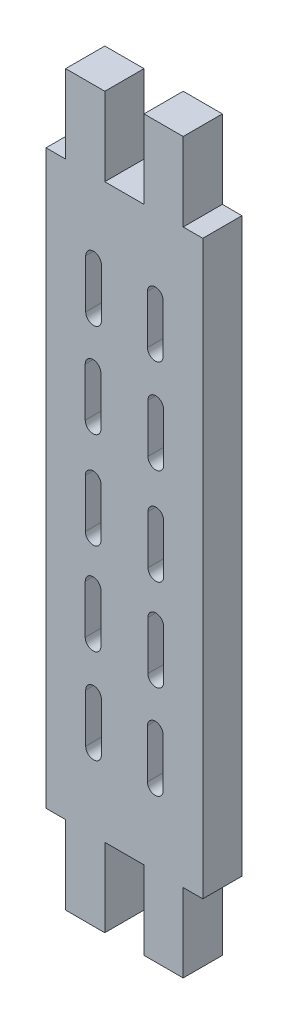
SolidWorks part; units mm, degrees
ref_plane "Front Plane" through (0, 0, 0) normal (0, 0, 1) x (1, 0, 0)
ref_plane "Top Plane" through (0, 0, 0) normal (0, 1, 0) x (1, 0, 0)
ref_plane "Right Plane" through (0, 0, 0) normal (1, 0, 0) x (0, 0, -1)
sketch "Sketch1" plane through (0, 0, 0) normal (0, 0, 1) x (1, 0, 0)
  line L0 (-7.5, 36.5) -> (-7.5, 46.5)
  line L1 (-10, -36.5) -> (-7.5, -36.5)
  line L2 (-10, -36.5) -> (-10, 36.5)
  line L3 (-10, 36.5) -> (-7.5, 36.5)
  line L4 (10, -36.5) -> (10, 36.5)
  line L5 (-10, -36.5) -> (10, 36.5) construction
  line L6 (-10, 36.5) -> (10, -36.5) construction
  line L7 (-7.5, 46.5) -> (-2.5, 46.5)
  line L8 (-2.5, 46.5) -> (-2.5, 36.5)
  line L9 (2.5, 36.5) -> (2.5, 46.5)
  line L10 (2.5, 46.5) -> (7.5, 46.5)
  line L11 (7.5, 46.5) -> (7.5, 36.5)
  line L12 (-2.5, 36.5) -> (2.5, 36.5)
  line L13 (7.5, 36.5) -> (10, 36.5)
  line L14 (-2.5, -36.5) -> (2.5, -36.5)
  line L16 (-7.5, -36.5) -> (-7.5, -41.5)
  line L20 (2.5, -36.5) -> (2.5, -46.5)
  line L23 (7.5, -36.5) -> (10, -36.5)
  line L24 (-7.5, -41.5) -> (-7.5, -46.5)
  line L25 (-7.5, -46.5) -> (-2.5, -46.5)
  line L26 (-2.5, -46.5) -> (-2.5, -36.5)
  line L28 (2.5, -46.5) -> (7.5, -46.5)
  line L29 (7.5, -46.5) -> (7.5, -36.5)
  line L30 (0, 0) -> (0, 42.4958) construction
  line L31 (0, 0) -> (41.6146, 0) construction
  line L32 (4, -15.1) -> (4, -8.9) construction
  line L35 (3, -15.1) -> (3, -8.9)
  line L38 (5, -15.1) -> (5, -8.9)
  line L41 (4, 15.1) -> (4, 8.9) construction
  line L44 (3, 15.1) -> (3, 8.9)
  line L51 (5, 15.1) -> (5, 8.9)
  line L52 (-4, 15.1) -> (-4, 8.9) construction
  line L53 (-3, 15.1) -> (-3, 8.9)
  line L54 (-5, 15.1) -> (-5, 8.9)
  line L55 (-4, -15.1) -> (-4, -8.9) construction
  line L56 (-3, -15.1) -> (-3, -8.9)
  line L57 (-5, -15.1) -> (-5, -8.9)
  line L58 (3.9391, 27.1) -> (3.9391, 20.9) construction
  line L61 (2.9391, 27.1) -> (2.9391, 20.9)
  line L64 (4.9391, 27.1) -> (4.9391, 20.9)
  line L67 (-3.9391, 27.1) -> (-3.9391, 20.9) construction
  line L68 (-2.9391, 27.1) -> (-2.9391, 20.9)
  line L69 (-4.9391, 27.1) -> (-4.9391, 20.9)
  line L70 (4.0117, 2.8029) -> (4.0117, -3.3971) construction
  line L71 (3.0117, 2.8029) -> (3.0117, -3.3971)
  line L72 (5.0117, 2.8029) -> (5.0117, -3.3971)
  line L73 (-3.9883, 2.8029) -> (-3.9883, -3.3971) construction
  line L74 (-2.9883, 2.8029) -> (-2.9883, -3.3971)
  line L75 (-4.9883, 2.8029) -> (-4.9883, -3.3971)
  line L76 (3.9391, -27.1) -> (3.9391, -20.9) construction
  line L77 (2.9391, -27.1) -> (2.9391, -20.9)
  line L78 (4.9391, -27.1) -> (4.9391, -20.9)
  line L79 (-3.9391, -27.1) -> (-3.9391, -20.9) construction
  line L80 (-2.9391, -27.1) -> (-2.9391, -20.9)
  line L81 (-4.9391, -27.1) -> (-4.9391, -20.9)
  line L82 (3.9391, 24) -> (21.2063, 24) construction
  line L83 (4, 12) -> (20.2276, 12) construction
  arc A29 (3, -15.1) -> (5, -15.1) centre (4, -15.1) ccw
  arc A30 (5, -8.9) -> (3, -8.9) centre (4, -8.9) ccw
  arc A33 (3, 15.1) -> (5, 15.1) centre (4, 15.1) cw
  arc A34 (5, 8.9) -> (3, 8.9) centre (4, 8.9) cw
  arc A35 (-3, 15.1) -> (-5, 15.1) centre (-4, 15.1) ccw
  arc A36 (-5, 8.9) -> (-3, 8.9) centre (-4, 8.9) ccw
  arc A37 (-3, -15.1) -> (-5, -15.1) centre (-4, -15.1) cw
  arc A38 (-5, -8.9) -> (-3, -8.9) centre (-4, -8.9) cw
  arc A45 (2.9391, 27.1) -> (4.9391, 27.1) centre (3.9391, 27.1) cw
  arc A46 (4.9391, 20.9) -> (2.9391, 20.9) centre (3.9391, 20.9) cw
  arc A47 (-2.9391, 27.1) -> (-4.9391, 27.1) centre (-3.9391, 27.1) ccw
  arc A48 (-4.9391, 20.9) -> (-2.9391, 20.9) centre (-3.9391, 20.9) ccw
  arc A49 (3.0117, 2.8029) -> (5.0117, 2.8029) centre (4.0117, 2.8029) cw
  arc A50 (5.0117, -3.3971) -> (3.0117, -3.3971) centre (4.0117, -3.3971) cw
  arc A51 (-2.9883, 2.8029) -> (-4.9883, 2.8029) centre (-3.9883, 2.8029) ccw
  arc A52 (-4.9883, -3.3971) -> (-2.9883, -3.3971) centre (-3.9883, -3.3971) ccw
  arc A53 (2.9391, -27.1) -> (4.9391, -27.1) centre (3.9391, -27.1) ccw
  arc A54 (4.9391, -20.9) -> (2.9391, -20.9) centre (3.9391, -20.9) ccw
  arc A55 (-2.9391, -27.1) -> (-4.9391, -27.1) centre (-3.9391, -27.1) cw
  arc A56 (-4.9391, -20.9) -> (-2.9391, -20.9) centre (-3.9391, -20.9) cw
  point P0 (0, 0)
  point P29 (4, -12)
  point P36 (4, 12)
  point P45 (-4, 12)
  point P52 (-4, -12)
  point P57 (3.9391, 24)
  point P65 (-3.9391, 24)
  point P72 (4.0117, -0.2971)
  point P78 (0, 0)
  point P79 (0, 0)
  point P80 (0, 0)
  point P83 (-3.9883, -0.2971)
  point P88 (3.9391, 27.1)
  point P91 (3.9391, -24)
  point P98 (-3.9391, -24)
  dimension "D8" = 1
  dimension "D9" = 6.2
  dimension "D12" = 12
  dimension "D1" = 5
  dimension "D2" = 5
  dimension "D3" = 20
  dimension "D4" = 10
  dimension "D5" = 73
  dimension "D6" = 5
  dimension "D7" = 10
  dimension "D10" = 4
  dimension "D11" = 12
extrude "Boss-Extrude1" add sketch "Sketch1" along normal blind 5 contours L28 L29 L23 L4 L13 L11 L10 L9 L12 L8 L7 L0 L3 L2 L1 L16 L24 L25 L26 L14 L20 A36 L54 A35 L53 A30 L38 A29 L35 L51 A34 L44 A33 L57 A38 L56 A37 region at (-0.0002, 0.0061, 0)
